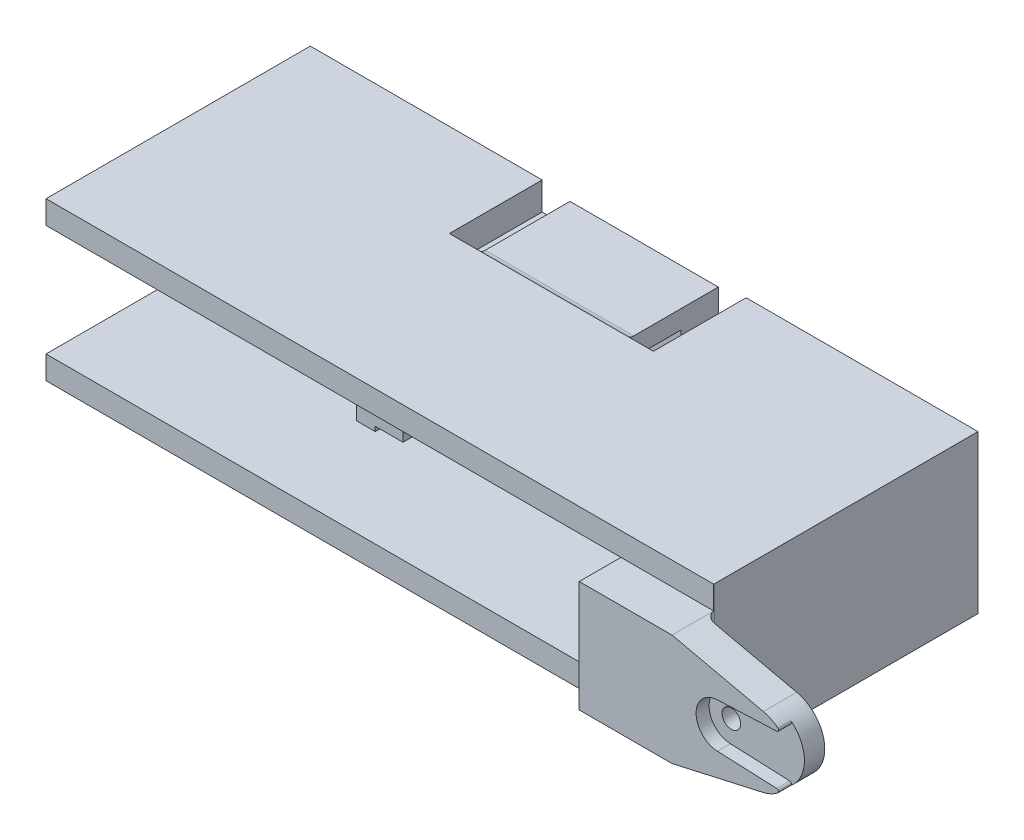
SolidWorks part; units mm, degrees
ref_plane "Front Plane" through (0, 0, 0) normal (0, 0, 1) x (1, 0, 0)
ref_plane "Top Plane" through (0, 0, 0) normal (0, 1, 0) x (1, 0, 0)
ref_plane "Right Plane" through (0, 0, 0) normal (1, 0, 0) x (0, 0, -1)
sketch "Sketch1" plane through (0, 0, 0) normal (0, 1, 0) x (1, 0, 0)
  line L1 (-36, 28.5) -> (36, 28.5)
  line L2 (-36, 28.5) -> (-36, 0)
  line L3 (-36, 0) -> (36, 0)
  line L4 (36, 28.5) -> (36, 0)
  point P4 (0, 0)
  dimension "D1" = 72
  dimension "D2" = 28.5
extrude "Boss-Extrude1" add sketch "Sketch1" along normal blind 8.5 and the other way blind 8.5
sketch "Sketch2" plane through (-36, 0, 0) normal (-1, 0, 0) x (0, 0, 1)
  line L0 (-28.5, 8.5) -> (0, 8.5) construction
  line L1 (-26.5, 6) -> (4.7015, 6)
  line L2 (-26.5, 6) -> (-26.5, -6)
  line L3 (-26.5, -6) -> (4.7015, -6)
  line L4 (4.7015, 6) -> (4.7015, -6)
  line L5 (-28.5, -8.5) -> (0, -8.5) construction
  line L6 (-28.5, -8.5) -> (-28.5, 8.5) construction
  dimension "D1" = 2.5
  dimension "D2" = 2.5
  dimension "D3" = 2
extrude "Cut-Extrude1" cut sketch "Sketch2" against normal offset from surface (69 mm away) 3 up to face at (36, 0, -14.25)
sketch "Sketch3" plane through (0, 0, 0) normal (0, 0, 1) x (1, 0, 0)
  line L0 (-36, -8.5) -> (36, -8.5) construction
  line L1 (36, 8.5) -> (26, 8.5)
  line L2 (36, 8.5) -> (36, -8.5)
  line L3 (36, -8.5) -> (26, -8.5)
  line L4 (26, 8.5) -> (26, -8.5)
  dimension "D1" = 10
extrude "Boss-Extrude2" add sketch "Sketch3" against normal blind 3 contours L2 L1 L4 L3
sketch "Sketch5" plane through (0, 0, 0) normal (0, 1, 0) x (1, 0, 0)
  line L0 (33, 26.5) -> (-36, 26.5) construction
  line L1 (33, 26.5) -> (-36, 26.5)
  line L2 (8.8399, -0.1) -> (-36.6153, -0.1) construction
  line L3 (-4.2693, -4.5) -> (41.533, -4.5) construction
  line L4 (41.533, -4.5) -> (41.533, -3.1) construction
  line L5 (41.533, -3.1) -> (-4.2693, -3.1) construction
  dimension "D1" = 26.6
  dimension "D2" = 31
  dimension "D3" = 1.4
sketch "Sketch6" plane through (0, 0, -28.5) normal (0, 0, -1) x (-1, 0, 0)
  line L0 (-8, 8) -> (8, -8) construction
  line L1 (-8, 8) -> (8, 8) construction
  line L2 (-8, 8) -> (-8, -8) construction
  line L3 (-8, -8) -> (8, -8) construction
  line L4 (8, 8) -> (8, -8) construction
  line L5 (-36, 0) -> (36, 0) construction
  line L6 (-36, -8.5) -> (-36, 8.5) construction
  line L7 (36, -8.5) -> (36, 8.5) construction
  line L8 (-11, 8.5) -> (-11, 5.5)
  line L9 (0, 0) -> (0, 21.0452) construction
  line L10 (-36, 8.5) -> (36, 8.5) construction
  line L11 (-11, -5.5) -> (-11, -8.5)
  line L12 (-36, -8.5) -> (36, -8.5) construction
  line L13 (11, -5.5) -> (11, -8.5)
  line L14 (11, 8.5) -> (11, 5.5)
  line L15 (-11, 5.5) -> (-8, 5.5)
  line L16 (-8, 5.5) -> (-8, 8)
  line L17 (-8, 8) -> (8, 8)
  line L18 (8, 8) -> (8, 5.5)
  line L19 (8, 5.5) -> (11, 5.5)
  line L20 (-11, 8.5) -> (11, 8.5)
  line L21 (-11, -8.5) -> (11, -8.5)
  line L22 (-11, -5.5) -> (-8, -5.5)
  line L23 (-8, -5.5) -> (-8, -8)
  line L24 (-8, -8) -> (8, -8)
  line L25 (8, -8) -> (8, -5.5)
  line L26 (8, -5.5) -> (11, -5.5)
  point P10 (0, 0)
  dimension "D1" = 16
  dimension "D2" = 22
  dimension "D3" = 3
extrude "Cut-Extrude2" cut sketch "Sketch6" against normal blind 10
fillet "Fillet1" radius 1 2 edges at (0, 8, -18.5) (0, -8, -18.5)
sketch "Sketch7" plane through (0, 0, -26.5) normal (0, 0, 1) x (1, 0, 0)
  line L0 (33, 6) -> (33, -6) construction
  line L1 (33, 6) -> (33, -6) construction
  line L2 (-11, -6) -> (-36, -6) construction
  line L3 (33, 6) -> (-13, 6)
  line L4 (33, 6) -> (33, -6)
  line L5 (33, -6) -> (-13, -6)
  line L6 (-13, 6) -> (-13, -6)
  line L7 (-36, 6) -> (-36, -6) construction
  line L8 (11, 6) -> (11, 5.5)
  line L9 (11, 5.5) -> (8, 5.5)
  line L10 (8, 5.5) -> (8, 6)
  line L11 (8, 5.5) -> (8, 6) construction
  line L12 (11, -6) -> (11, -5.5)
  line L13 (11, -5.5) -> (8, -5.5)
  line L14 (8, -5.5) -> (11, -5.5) construction
  line L15 (8, -5.5) -> (8, -6)
  line L16 (8, -6) -> (8, -5.5) construction
  line L17 (-11, 6) -> (-11, 5.5)
  line L18 (-11, 5.5) -> (-8, 5.5)
  line L19 (-8, 5.5) -> (-8, 6)
  line L20 (-11, -6) -> (-11, -5.5)
  line L21 (-11, -5.5) -> (-8, -5.5)
  line L22 (-8, -5.5) -> (-8, -6)
  line M7 (11, 5.5) -> (8, 5.5)
  line M8 (8, 5.5) -> (8, 6)
  line M9 (8, 6) -> (-8, 6)
  line M10 (-8, 6) -> (-8, 5.5)
  line M18 (-8, -5.5) -> (-8, -6)
  line M19 (-8, -6) -> (8, -6)
  line M20 (8, -6) -> (8, -5.5)
  line M21 (8, -5.5) -> (11, -5.5)
  line M22 (11, -5.5) -> (11, -6)
  line M23 (11, -6) -> (33, -6)
  line M24 (33, -6) -> (33, 6)
  line M25 (33, 6) -> (11, 6)
  line M26 (11, 6) -> (11, 5.5)
  dimension "D1" = 23
extrude "Boss-Extrude3" add sketch "Sketch7" along normal blind 2 contours L6 M10 M18 M19 M20 M21 M22 M23 M24 M25 M26 M7 M8 M9 region at (10.1099, 0, -26.5)
sketch "Sketch8" plane through (0, 0, -28.5) normal (0, 0, -1) x (-1, 0, 0)
  line L0 (-8, 5.5) -> (-8, 8) construction
  line L1 (-6.4, 6.4) -> (6.4, 6.4)
  line L2 (-6.4, 6.4) -> (-6.4, -6.4)
  line L3 (-6.4, -6.4) -> (6.4, -6.4)
  line L4 (6.4, 6.4) -> (6.4, -6.4)
  line L5 (-8, 8) -> (8, 8) construction
  line L6 (8, 8.5) -> (8, 6) construction
  line L7 (8, -8) -> (-8, -8) construction
  circle A0 centre (0, 0) radius 3.26
  circle A1 centre (0, 0) radius 2.4
  dimension "D5" = 6.52
  dimension "D6" = 4.8
  dimension "D1" = 1.6
  dimension "D2" = 1.6
  dimension "D3" = 1.6
  dimension "D4" = 1.6
extrude "Cut-Extrude3" cut sketch "Sketch8" against normal blind 2 contours L4 L1 L2 L3 A0 | A1 region at (0, 6.219, -28.5) region at (0, 0, -28.5)
sketch "Sketch9" plane through (0, 0, 0) normal (0, 0, 1) x (1, 0, 0)
  line L0 (-36, -8.5) -> (36, -8.5) construction
  line L1 (36, 8.5) -> (26, 8.5)
  line L2 (36, 8.5) -> (36, -8.5)
  line L3 (36, -8.5) -> (26, -8.5)
  line L4 (26, 8.5) -> (26, -8.5)
  line L5 (26, 6) -> (26, -6) construction
ref_plane "Plane1" through (0, 0, 3.1) normal (0, 0, 1) x (1, 0, 0)
sketch "Sketch11" plane through (0, 0, 3.1) normal (0, 0, 1) x (1, 0, 0)
  line L0 (26, 8.5) -> (36, -8.5) construction
  line L1 (26, 8.5) -> (26, -8.5) construction
  line L2 (26, 6) -> (52, 6)
  line L3 (26, 6) -> (26, -6)
  line L4 (26, -6) -> (52, -6)
  line L5 (52, 6) -> (52, -6)
  line L6 (52, 0) -> (26, 0) construction
  line L7 (36, 8.5) -> (36, -8.5) construction
  point P7 (31, 0)
  dimension "D1" = 16
  dimension "D2" = 12
sketch3d "3DSketch1" [suppressed]
  line L0 (36, -9.1, 0) -> (52, -6.05, 4.7)
  line L1 (22.8, -6.05, 4.7) -> (22.8, -9.1, 0)
  line L2 (36, 9, 0) -> (52, 5.95, 4.7)
  line L3 (22.8, 9, 0) -> (22.8, 5.95, 4.7)
extrude "Boss-Extrude7" add sketch "Sketch11" against normal up to surface (3.1 mm away) up to face at (-2.5, 0, 0)
fillet "Fillet3" [suppressed] radius 2
sketch "Sketch14" plane through (0, 0, 3.1) normal (0, 0, 1) x (1, 0, 0)
  line L0 (26, 0) -> (52, 0) construction
  line L1 (26, 6) -> (26, -6) construction
  line L2 (52, -6) -> (52, 6) construction
  circle A0 centre (49, 0) radius 1 construction
  circle A5 centre (45, 0) radius 1 construction
  circle A6 centre (41, 0) radius 1
  circle A7 centre (37, 0) radius 1 construction
  dimension "D1" = 2
  dimension "D4" = 4
  dimension "D2" = 3
  dimension "D3" = 4
extrude "Cut-Extrude4" cut sketch "Sketch14" against normal through all
sketch "Sketch15" plane through (0, 0, 3.1) normal (0, 0, 1) x (1, 0, 0)
  line L0 (36, 6) -> (50.8333, 2.6625)
  line L1 (52, 6) -> (26, 6) construction
  line L2 (52, -6) -> (52, 6) construction
  line L3 (36, 6) -> (52, 6)
  line L4 (52, 6) -> (52, -6)
  line L5 (52, -6) -> (36, -6)
  line L6 (36, -6) -> (51.1381, -2.5939)
  circle A0 centre (49, 0) radius 3
  line M10 (52, 6) -> (26, 6)
extrude "Cut-Extrude6" cut sketch "Sketch15" against normal through all contours A0 L4 L0 M10 region at (46.8484, 4.6943, 3.1)
sketch "Sketch17" plane through (0, 0, 3.1) normal (0, 0, 1) x (1, 0, 0)
  line L0 (52, -6) -> (36, -6) construction
  line L1 (52, 6) -> (52, -6) construction
  line L2 (36, -6) -> (51.1381, -2.5939) construction
  line L3 (52, -6) -> (36, -6)
  line L4 (52, 6) -> (52, -6)
  line L5 (36, -6) -> (51.1381, -2.5939)
  circle A0 centre (49, 0) radius 3 construction
  circle A1 centre (49, 0) radius 3
  line M5 (52, -6) -> (52, 0)
  line M10 (26, -6) -> (52, -6)
extrude "Cut-Extrude7" cut sketch "Sketch17" against normal through all contours A1 L5 M10 M5 region at (46.8484, -4.6943, 3.1)
sketch "Sketch18" plane through (0, 0, -24.5) normal (0, 0, 1) x (1, 0, 0)
  line L0 (-8, -6) -> (8, -6) construction
  line L1 (-13, 6) -> (-8, 6)
  line L2 (-13, 6) -> (-13, -6)
  line L3 (-13, -6) -> (-8, -6)
  line L4 (-8, 6) -> (-8, -6)
  line L5 (-11, 6) -> (-11, 5.5)
  line L6 (-11, 5.5) -> (-8, 5.5)
  line L7 (-8, 5.5) -> (-11, 5.5) construction
  line L8 (-11, -6) -> (-11, -5.5)
  line L9 (-11, -5.5) -> (-8, -5.5)
  line L10 (-11, -5.5) -> (-8, -5.5) construction
  line M3 (-11, 6) -> (-13, 6)
  line M4 (-13, 6) -> (-13, -6)
  line M5 (-13, -6) -> (-11, -6)
  line M6 (-11, -6) -> (-11, -5.5)
  line M7 (-11, -5.5) -> (-8, -5.5)
  line M21 (-8, 5.5) -> (-11, 5.5)
  line M22 (-11, 5.5) -> (-11, 6)
  dimension "D1" = 5
extrude "Boss-Extrude8" add sketch "Sketch18" along normal blind 14 contours L4 M21 M22 M3 M4 M5 M6 M7 region at (-10.5526, 0, -24.5)
sketch "Sketch19" plane through (0, 0, -10.5) normal (0, 0, 1) x (1, 0, 0)
  line L0 (-10.25, 0) -> (0, 0) construction
  line L1 (-13, 6) -> (-13, -6) construction
  circle A0 centre (-10.25, 0) radius 1
  dimension "D1" = 2
  dimension "D2" = 2.75
extrude "Cut-Extrude8" cut sketch "Sketch19" against normal blind 5
sketch "Sketch20" plane through (0, -8.5, 0) normal (0, -1, 0) x (1, 0, 0)
  line L0 (36, 0) -> (36, 3.1) construction
  line L1 (36, 0.9) -> (53.876, 0.9)
  line L2 (36, 0.9) -> (36, -4.9671)
  line L3 (36, -4.9671) -> (53.876, -4.9671)
  line L4 (53.876, 0.9) -> (53.876, -4.9671)
  line L5 (36, 3.1) -> (49.6585, 3.1) construction
  dimension "D1" = 2.2
extrude "Cut-Extrude9" cut sketch "Sketch20" against normal through all
fillet "Fillet4" radius 1 1 edges at (36, 0, 0.9)
sketch "Sketch21" plane through (0, 0, 3.1) normal (0, 0, 1) x (1, 0, 0)
  line L0 (36, 6) -> (49.6585, 2.9268) construction
  line L1 (36, -6) -> (49.6585, -2.9268) construction
  line L2 (36, -6) -> (49.6585, -2.9268)
  line L3 (36, 6) -> (49.6585, 2.9268)
  circle A0 centre (45, 0) radius 3.878
  arc A1 (49.6585, -2.9268) -> (49.6585, 2.9268) centre (49, 0) ccw construction
  arc A2 (49.6585, -2.9268) -> (49.6585, 2.9268) centre (49, 0) ccw
  arc M6 (49.6585, -2.9268) -> (49.6585, 2.9268) centre (49, 0) ccw
  line M7 (49.6585, 2.9268) -> (36, 6)
extrude "Cut-Extrude10" cut sketch "Sketch21" against normal blind 10 contours A0 L2 M6 M7 region at (49.804, 0, 3.1)
sketch "Sketch22" plane through (0, 0, 3.1) normal (0, 0, 1) x (1, 0, 0)
  line L0 (40.2259, 1.9685) -> (52.5505, 2.5)
  line L1 (41, 0) -> (55, 0) construction
  line L2 (40.2259, -1.9685) -> (52.5505, -2.5)
  line L3 (52.5505, 2.5) -> (52.5505, -2.5)
  circle A0 centre (41, 0) radius 2
  circle A1 centre (55, 0) radius 3.5
  dimension "D1" = 7
  dimension "D3" = 4
  dimension "D2" = 14
  dimension "D4" = 5
sketch "Sketch23" plane through (0, 0, 3.1) normal (0, 0, 1) x (1, 0, 0)
  line L0 (40.2945, 2.3718) -> (51.9131, 2.8729)
  line L2 (40.2259, 1.9685) -> (52.5505, 2.5) construction
  line L3 (41, 0) -> (55, 0) construction
  line L4 (40.2945, -2.3718) -> (51.9131, -2.8729)
  line L5 (26, 6) -> (26, -6) construction
  line L6 (36, -6) -> (26, -6) construction
  line L7 (36, -6) -> (45.8513, -3.7835) construction
  line L8 (36, 6) -> (26, 6) construction
  line L9 (36, 6) -> (45.8513, 3.7835) construction
  line L10 (26, 6) -> (26, -6)
  line L11 (36, -6) -> (26, -6)
  line L12 (36, -6) -> (45.8513, -3.7835)
  line L13 (36, 6) -> (26, 6)
  line L14 (36, 6) -> (45.8513, 3.7835)
  circle A0 centre (41, 0) radius 2.4
  circle A1 centre (41, 0) radius 2 construction
  arc A2 (45.8513, -3.7835) -> (45.8513, 3.7835) centre (45, 0) ccw construction
  arc A3 (45.8513, -3.7835) -> (45.8513, 3.7835) centre (45, 0) ccw
  line M5 (36, -6) -> (45.8513, -3.7835)
  arc M6 (45.8513, -3.7835) -> (45.8513, 3.7835) centre (45, 0) ccw
  line M7 (45.8513, 3.7835) -> (36, 6)
  line M8 (36, 6) -> (26, 6)
  line M9 (26, 6) -> (26, -6)
  line M10 (26, -6) -> (36, -6)
  dimension "D1" = 0.4
extrude "Boss-Extrude9" add sketch "Sketch23" along normal blind 1.4 contours A0 L0 L4 M6 M7 M8 M9 M10 M5 region at (34.1186, 0, 3.1)
fillet "Fillet5" radius 0.2 2 edges at (47.7886, -2.695, 3.8) (47.7886, 2.695, 3.8)
